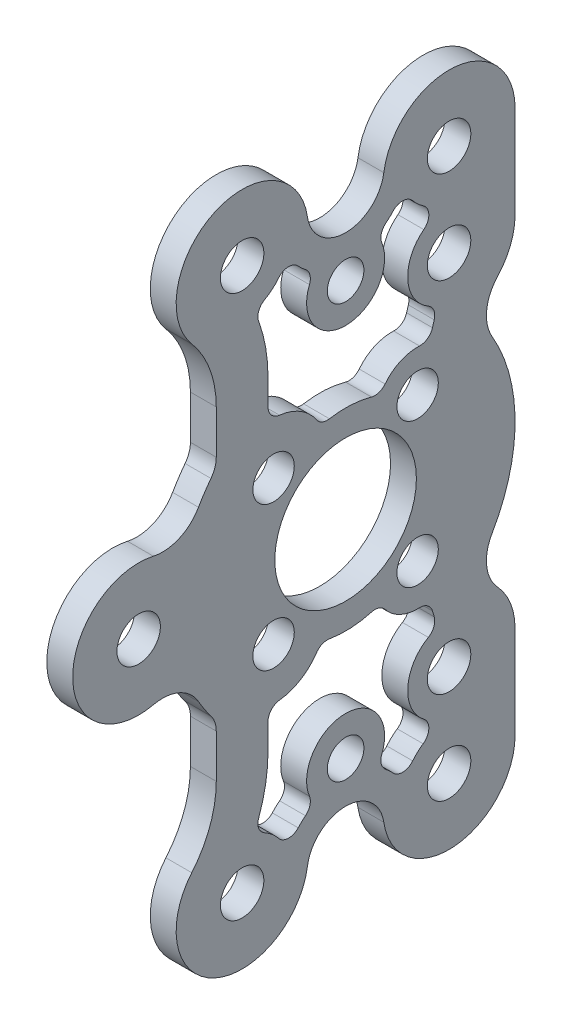
SolidWorks part; units mm, degrees
material "AR500"
ref_plane "Front Plane" through (0, 0, 0) normal (0, 0, 1) x (1, 0, 0)
ref_plane "Top Plane" through (0, 0, 0) normal (0, 1, 0) x (1, 0, 0)
ref_plane "Right Plane" through (0, 0, 0) normal (1, 0, 0) x (0, 0, -1)
ref_plane "Motor Front Plane" through (39.075, 0, 0) normal (1, 0, 0) x (0, 0, -1)
sketch "Sketch1" plane through (39.075, 0, 0) normal (1, 0, 0) x (0, 0, -1)
  line L1 (12.7, 21.997) -> (-25.4, 0) construction
  line L3 (12.7, 21.997) -> (12.7, -21.997) construction
  line L4 (-25.4, 0) -> (12.7, -21.997) construction
  line L5 (20.8, 21.997) -> (20.8, 32.6221) construction
  circle A0 centre (8.8388, -8.8388) radius 1.65 construction
  circle A1 centre (8.8388, 8.8388) radius 1.65 construction
  circle A2 centre (-8.8388, -8.8388) radius 1.65 construction
  circle A3 centre (-8.8388, 8.8388) radius 1.65 construction
  circle A4 centre (8.8388, -8.8388) radius 1.65 construction
  circle A5 centre (8.8388, 8.8388) radius 1.65 construction
  circle A6 centre (-8.8388, -8.8388) radius 1.65 construction
  circle A7 centre (-8.8388, 8.8388) radius 1.65 construction
  circle A8 centre (0, 0) radius 20.8 construction
  circle A9 centre (0, 0) radius 8.69
  circle A10 centre (-8.8388, 8.8388) radius 2.54
  circle A11 centre (8.8388, 8.8388) radius 2.54
  circle A12 centre (8.8388, -8.8388) radius 2.54
  circle A13 centre (-8.8388, -8.8388) radius 2.54
  circle A14 centre (-8.8388, 8.8388) radius 3.81 construction
  circle A16 centre (12.7, 21.997) radius 2.667
  circle A18 centre (12.7, -21.997) radius 2.667
  circle A19 centre (-25.4, 0) radius 2.667
  arc A20 (-19.925, -5.9695) -> (4.7928, -20.2403) centre (0, 0) ccw
  arc A21 (-19.925, 5.9695) -> (4.7928, 20.2403) centre (0, 0) cw
  arc A23 (15.1322, 14.2708) -> (15.1322, -14.2708) centre (0, 0) cw
  arc A24 (-19.925, -5.9695) -> (-19.925, 5.9695) centre (-25.4, 0) cw
  arc A25 (4.7928, 20.2403) -> (15.1322, 14.2708) centre (12.7, 21.997) cw
  arc A27 (4.7928, -20.2403) -> (15.1322, -14.2708) centre (12.7, -21.997) ccw
  circle A28 centre (0, 0) radius 25.4 construction
  dimension "D1" = 41.6
  dimension "D2" = 5.08
  dimension "D3" = 7.62
  dimension "D4" = 5.334
  dimension "D5" = 50.8
extrude "Boss-Extrude1" add sketch "Sketch1" along normal blind 3.175
fillet "Fillet1" radius 5.08 6 edges at (40.6625, 5.9695, 19.925) (40.6625, -14.2708, -15.1322) (40.6625, -20.2403, -4.7928) (40.6625, -5.9695, 19.925) (40.6625, 20.2403, -4.7928) (40.6625, 14.2708, -15.1322)
sketch "Sketch2" plane through (42.25, 0, 0) normal (1, 0, 0) x (0, 0, -1)
  line L0 (-12.7, -33.3375) -> (-12.7, 33.3375) construction
  line L5 (0, 0) -> (-12.7, 0) construction
  line L6 (0, 0) -> (0, 30.48) construction
  line L11 (12.7, 33.3375) -> (12.7, 21.997) construction
  line L13 (20.8, 33.3375) -> (20.8, 21.997)
  line L14 (-15.875, 19.8978) -> (-15.875, 13.4397)
  line L15 (11.7095, 24.4733) -> (-15.875, 13.4397)
  arc A24 (-4.6874, 34.5243) -> (-18.8821, 28.1038) centre (-12.7, 33.3375) ccw
  circle A27 centre (-12.7, 33.3375) radius 2.667
  circle A32 centre (12.7, 33.3375) radius 2.667
  arc A33 (4.6874, 34.5243) -> (20.8, 33.3375) centre (12.7, 33.3375) cw
  circle A34 centre (-25.4, 0) radius 2.667 construction
  arc A35 (-4.6874, 34.5243) -> (4.6874, 34.5243) centre (0, 35.2185) ccw
  arc A39 (18.6368, 16.4866) -> (4.9595, 24.3833) centre (12.7, 21.997) ccw construction
  arc A40 (-18.8821, 28.1038) -> (-15.875, 19.8978) centre (-28.575, 19.8978) cw
  arc A41 (0.0843, 20.7998) -> (-18.0553, 10.3269) centre (0, 0) ccw construction
  arc A42 (20.8, 21.997) -> (11.7095, 24.4733) centre (14.614, 17.2119) ccw
  circle A43 centre (12.7, 21.997) radius 2.667 construction
  dimension "D3" = 30.48
  dimension "D1" = 6.35
  dimension "D4" = 12.7
  dimension "D2" = 66.675
extrude "Boss-Extrude2" add sketch "Sketch2" against normal up to surface (3.175 mm away) up to face at (39.075, -21.997, -15.367)
sketch "Sketch3" plane through (39.075, 0, 0) normal (-1, 0, 0) x (0, 0, 1)
  line L0 (-11.2696, 17.1226) -> (-10.2692, 13.7133)
  line L1 (-12.7, 33.3375) -> (-12.7, 21.997)
  line L2 (9.525, 15.1517) -> (9.525, 19.8978)
  line L3 (15.875, 19.8978) -> (15.875, 13.4397) construction
  circle A0 centre (-12.7, 21.997) radius 5.08
  circle A1 centre (-8.8388, 8.8388) radius 5.08
  circle A2 centre (8.8388, 8.8388) radius 6.35
  circle A3 centre (12.7, 33.3375) radius 5.715
  circle A4 centre (-12.7, 33.3375) radius 5.715
  arc A5 (-7.1743, 31.8788) -> (7.1743, 31.8788) centre (0, 35.2185) ccw
  arc A6 (-4.6874, 34.5243) -> (4.6874, 34.5243) centre (0, 35.2185) ccw construction
  arc A7 (-9.5127, 28.5938) -> (-9.597, 26.0192) centre (-8.6273, 27.2762) ccw
  circle A8 centre (0, 0) radius 11.865
  circle A9 centre (0, 0) radius 8.69 construction
  arc A10 (9.525, 19.8978) -> (11.2461, 27.8105) centre (28.575, 19.8978) cw
  arc A11 (18.8821, 28.1038) -> (15.875, 19.8978) centre (28.575, 19.8978) ccw construction
  dimension "D1" = 11.43
  dimension "D2" = 10.16
  dimension "D3" = 3.175
  dimension "D4" = 1.5875
  dimension "D5" = 3.175
  dimension "D7" = 12.7
  dimension "D6" = 6.35
extrude "Cut-Extrude1" cut sketch "Sketch3" against normal through all contours L2 A10 A3 A5 A4 A7 A0 L0 A1 A8 A2 region at (39.075, 20.9217, 0.0796)
sketch "Sketch4" plane through (39.075, 0, 0) normal (-1, 0, 0) x (0, 0, 1)
  line L0 (0, 0) -> (0, 25.4) construction
  line L1 (0, 0) -> (21.997, 12.7) construction
  line L2 (15.875, 19.8978) -> (15.875, 13.4397) construction
  circle A0 centre (0, 25.4) radius 2.2479 construction
  circle A1 centre (0, 25.4) radius 4.7879
  circle A2 centre (0, 25.4) radius 3.9624 construction
  arc A4 (26.1205, 10.2667) -> (18.5916, 16.0656) centre (21.997, 12.7) ccw construction
  arc A5 (15.875, 17.1815) -> (18.5916, 16.0656) centre (17.4625, 17.1815) ccw construction
  arc A6 (26.1205, 10.2667) -> (27.1456, 7.9097) centre (27.4877, 9.4599) ccw construction
  arc A7 (23.5962, -7.8966) -> (23.5962, 7.8966) centre (25.4, 0) ccw construction
  arc A8 (15.875, 17.1815) -> (27.1456, 7.9097) centre (21.3119, 12.3044) ccw construction
  dimension "D1" = 4.4958
  dimension "D2" = 2.54
  dimension "D3" = 7.9248
  dimension "D6" = 1.5875
  dimension "D4" = 25.4
  dimension "D5" = 60
extrude "Boss-Extrude3" add sketch "Sketch4" against normal up to surface (3.175 mm away) up to face at (42.25, 21.997, -15.367)
sketch "Sketch7" plane through (39.075, 0, 0) normal (-1, 0, 0) x (0, 0, 1)
  point P0 (0, 25.4)
hole_wizard "#8 Clearance Hole1" positions "Sketch7" profile "Sketch6" hole size "#8" standard "ANSI Inch" end condition up to next
sketch "Sketch6" plane through (39.075, 25.4, 0) normal (0, 1, 0) x (0, 0, 1)
  line L0 (0, 0) -> (0, 3.175)
  line L1 (0, 3.175) -> (2.2479, 3.175)
  line L2 (2.2479, 3.175) -> (2.2479, 0)
  line L5 (2.2479, 0) -> (0, 0)
  line L11 (0, -6.35) -> (0, 107.95) construction
  dimension "Thru Hole Dia." = 4.4958
  dimension "Thru Hole Depth" = 3.175
fillet "Fillet3" radius 1.5875 10 edges at (40.6625, 11.4644, 3.0571) (40.6625, 11.0684, -4.2742) (40.6625, 13.7133, -10.2692) (40.6625, 17.1226, -11.2696) (40.6625, 31.8788, 7.1743) (40.6625, 27.8105, 11.2461) (40.6625, 15.1517, 9.525) (40.6625, 31.8788, -7.1743) (40.6625, 28.2876, -3.8191) (40.6625, 28.2876, 3.8191)
mirror "Mirror1" about plane through (0, 0, 0) normal (0, 1, 0) of "#8 Clearance Hole1", "Cut-Extrude1", "Fillet3", "Boss-Extrude2", "Boss-Extrude3"
fillet "Fillet4" radius 3.175 2 edges at (40.6625, -13.4397, 15.875) (40.6625, 13.4397, 15.875)
equation "\"D1@Sketch1\"=41.6mm"
